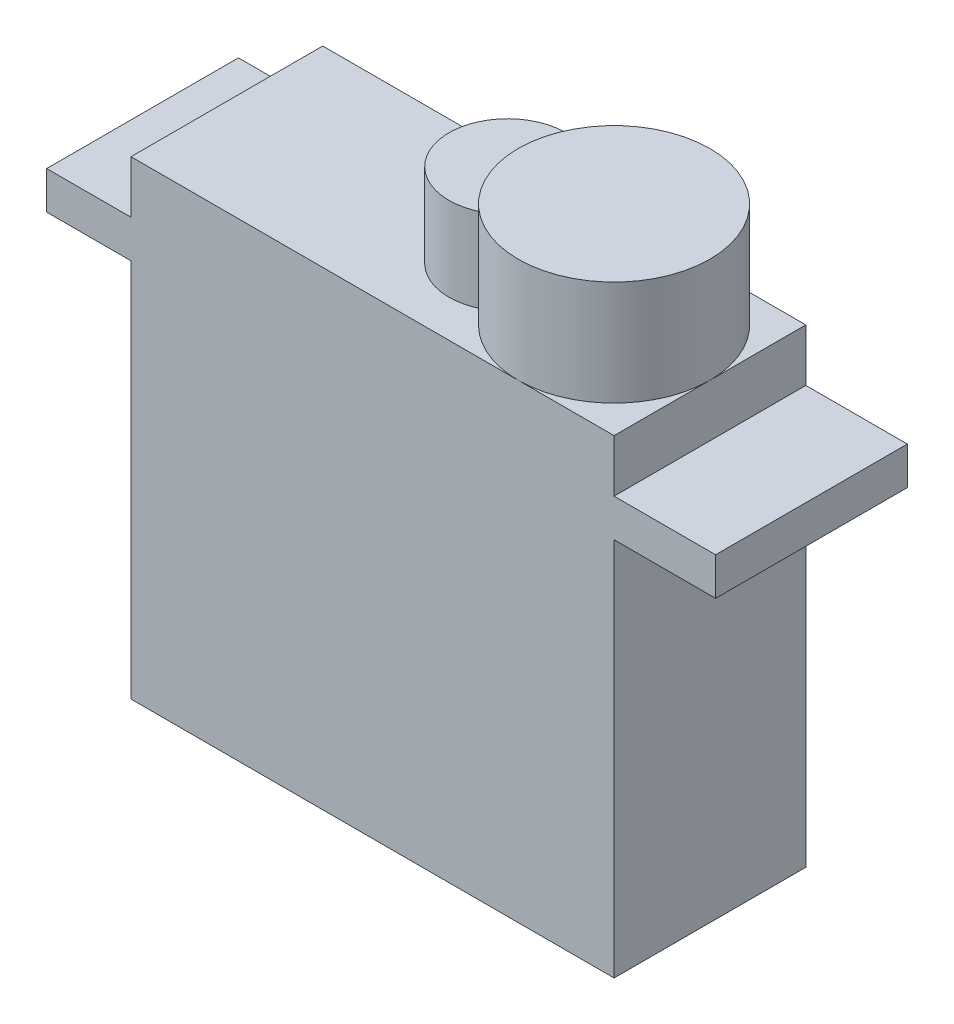
SolidWorks part; units mm, degrees
material "Delrin 2700 NC010, Low Viscosity Acetal Copolymer (SS)"
ref_plane "Front Plane" through (0, 0, 0) normal (0, 0, 1) x (1, 0, 0)
ref_plane "Top Plane" through (0, 0, 0) normal (0, 1, 0) x (1, 0, 0)
ref_plane "Right Plane" through (0, 0, 0) normal (1, 0, 0) x (0, 0, -1)
sketch "Sketch1" plane through (0, 0, 0) normal (0, 1, 0) x (1, 0, 0)
  line L1 (0, 0) -> (23.0378, 0)
  line L2 (0, 0) -> (0, 9.144)
  line L3 (0, 9.144) -> (23.0378, 9.144)
  line L4 (23.0378, 0) -> (23.0378, 9.144)
  dimension "D1" = 23.0378
  dimension "D2" = 9.144
extrude "Boss-Extrude1" add sketch "Sketch1" against normal blind 18.1
sketch "Sketch2" plane through (0, 0, 0) normal (0, 1, 0) x (1, 0, 0)
  line L0 (23.0378, 9.144) -> (0, 9.144) construction
  line L1 (-4.021, 9.144) -> (27.879, 9.144)
  line L2 (-4.021, 9.144) -> (-4.021, 0)
  line L3 (-4.021, 0) -> (27.879, 0)
  line L4 (27.879, 9.144) -> (27.879, 0)
  dimension "D1" = 9.144
  dimension "D2" = 31.9
extrude "Boss-Extrude2" add sketch "Sketch2" along normal blind 1.8
sketch "Sketch3" plane through (0, 1.8, 0) normal (0, 1, 0) x (1, 0, 0)
  line L0 (27.879, 9.144) -> (-4.021, 9.144) construction
  line L1 (0, 0) -> (23.0378, 0)
  line L2 (0, 0) -> (0, 9.144)
  line L3 (0, 9.144) -> (23.0378, 9.144)
  line L4 (23.0378, 0) -> (23.0378, 9.144)
  line L5 (-4.021, 0) -> (27.879, 0) construction
  dimension "D1" = 23.0378
extrude "Boss-Extrude3" add sketch "Sketch3" along normal blind 2.5
sketch "Sketch4" plane through (0, 4.3, 0) normal (0, 1, 0) x (1, 0, 0)
  circle A0 centre (18.4658, 4.572) radius 4.572
  dimension "D1" = 9.144
extrude "Boss-Extrude4" add sketch "Sketch4" along normal blind 5
sketch "Sketch5" plane through (0, 4.3, 0) normal (0, 1, 0) x (1, 0, 0)
  circle A0 centre (13.3858, 4.572) radius 2.794
  circle A1 centre (18.4658, 4.572) radius 4.572 construction
  circle A2 centre (18.4658, 4.572) radius 4.572 construction
  dimension "D2" = 5.588
  dimension "D1" = 5.08
extrude "Boss-Extrude5" add sketch "Sketch5" along normal blind 4
ref_axis "Axis1" through (18.4658, 9.3, -4.572) along (0, -1, 0)
move or copy body "Body-Move/Copy1" [suppressed] bodies to move or copy 105
